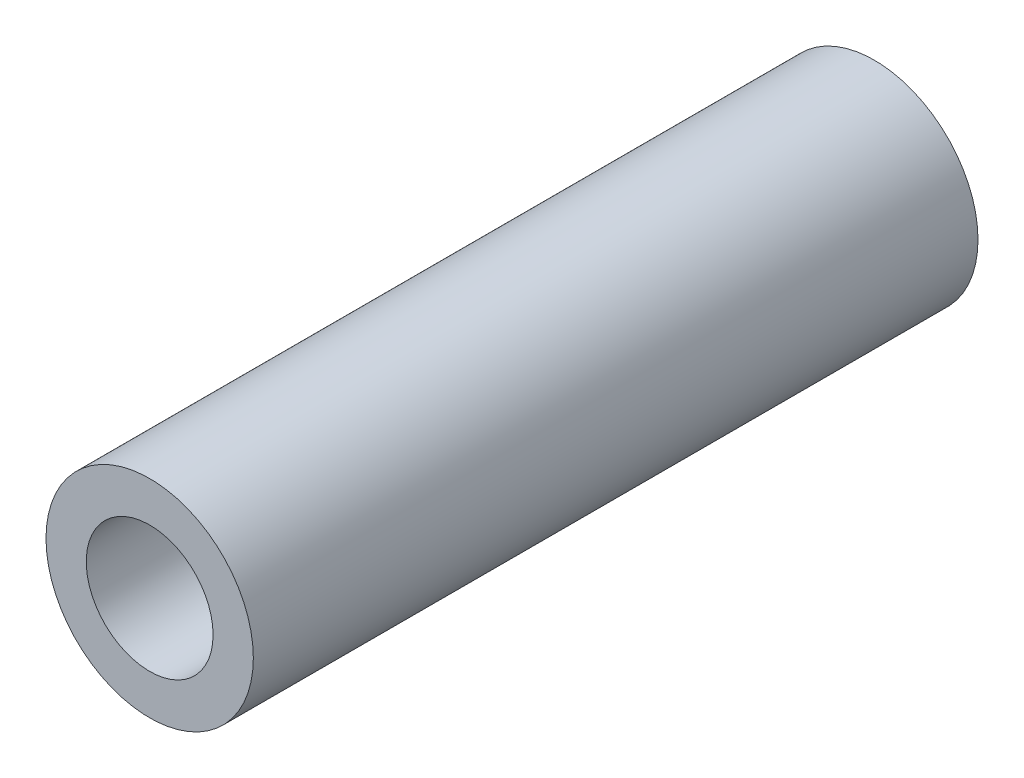
SolidWorks part; units mm, degrees
material "ABS"
ref_plane "Front Plane" through (0, 0, 0) normal (0, 0, 1) x (1, 0, 0)
ref_plane "Top Plane" through (0, 0, 0) normal (0, 1, 0) x (1, 0, 0)
ref_plane "Right Plane" through (0, 0, 0) normal (1, 0, 0) x (0, 0, -1)
sketch "Sketch1" plane through (0, 0, 0) normal (0, 0, 1) x (1, 0, 0)
  circle A0 centre (32.5, 0) radius 2.575
  point P3 (0, 0)
  point P4 (0, 0)
  point P5 (0, 0)
  point P6 (0, 0)
  point P7 (0, 0)
  point P8 (0, 0)
  dimension "D1" = 5.15
extrude "Boss-Extrude1" add sketch "Sketch1" along normal blind 18
sketch "Sketch3" plane through (0, 0, 18) normal (0, 0, 1) x (1, 0, 0)
  circle A0 centre (32.5, 0) radius 1.575
  circle A1 centre (32.5, 0) radius 2.1
  dimension "D1" = 3.15
  dimension "D2" = 4.2
extrude "Cut-Extrude1" cut sketch "Sketch3" against normal up to next contours A0
equation "\"RingPostIn\"=5.15"
equation "\"D1@Sketch1\"=\"RingPostIn\""
equation "\"RingPinShaft\"= 5.05"
equation "\"CenterBearingOut\"=32.00"
equation "\"m3Thru\"=3.15"
equation "\"D1@Sketch3\"=\"m3Thru\""
equation "\"m3Insert\"=4.2"
equation "\"D2@Sketch3\"=\"m3Insert\""
